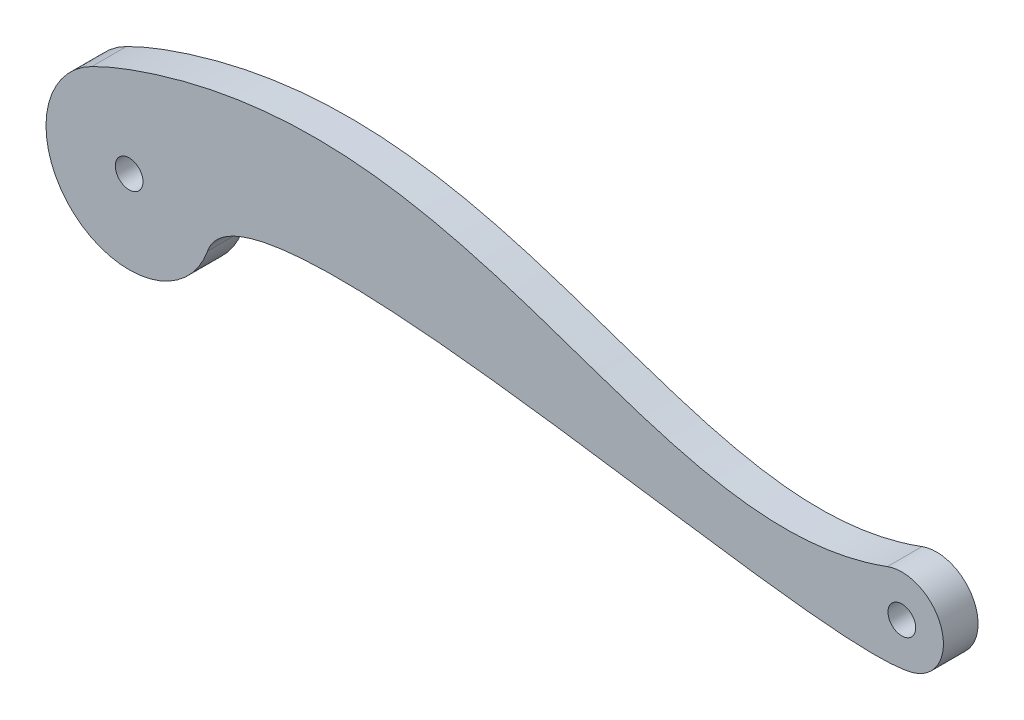
SolidWorks part; units mm, degrees
material "Thornel Mat VMA"
ref_plane "前视基准面" through (0, 0, 0) normal (0, 0, 1) x (1, 0, 0)
ref_plane "上视基准面" through (0, 0, 0) normal (0, 1, 0) x (1, 0, 0)
ref_plane "右视基准面" through (0, 0, 0) normal (1, 0, 0) x (0, 0, -1)
sketch "草图1" plane through (0, 0, 0) normal (0, 0, 1) x (1, 0, 0)
  line L0 (0, 0) -> (7.7715, -6.2932) construction
  line L2 (-10, 0) -> (0, 0) construction
  line L4 (0, 0) -> (114, 0) construction
  line L6 (0, 0) -> (11.3131, -4.0017) construction
  line L7 (109.4171, 5.6269) -> (111.5, 0) construction
  line L8 (111.5, 0) -> (114.5, -5.1962) construction
  circle A2 centre (0, 0) radius 2
  circle A3 centre (111.5, 0) radius 2
  circle A4 centre (0, 0) radius 12
  circle A5 centre (111.5, 0) radius 6
  circle A6 centre (0, 0) radius 10 construction
  spline S0 degree 3 poles (11.3131, -4.0017) (17.2885, 12.8913) (104.2661, -11.7075) (114.5, -5.1962) knots 0 0 0 0 0.832682 0.832682 0.832682 0.832682
  spline S1 degree 3 poles (-5.3862, 10.7233) (-2.8446, 11.9999) (48.9467, 31.7787) (75.6738, -6.8638) (109.4171, 5.6269) knots 0 0 0 0 0.036558 0.731169 0.731169 0.731169 0.731169
  dimension "D1" = 111.5
  dimension "D3" = 4
  dimension "D4" = 4
  dimension "D5" = 12
  dimension "D2" = 24
  dimension "D6" = 20
  dimension "D11" = 120
  dimension "D8" = 0
  dimension "D9" = 39
extrude "凸台-拉伸1" add sketch "草图1" along normal blind 5 contours A4 A2 | S1 A4 S0 A5 | A5 A3 region at (11.4925, -1.9727, 0) region at (54.7373, 5.6944, 0)
